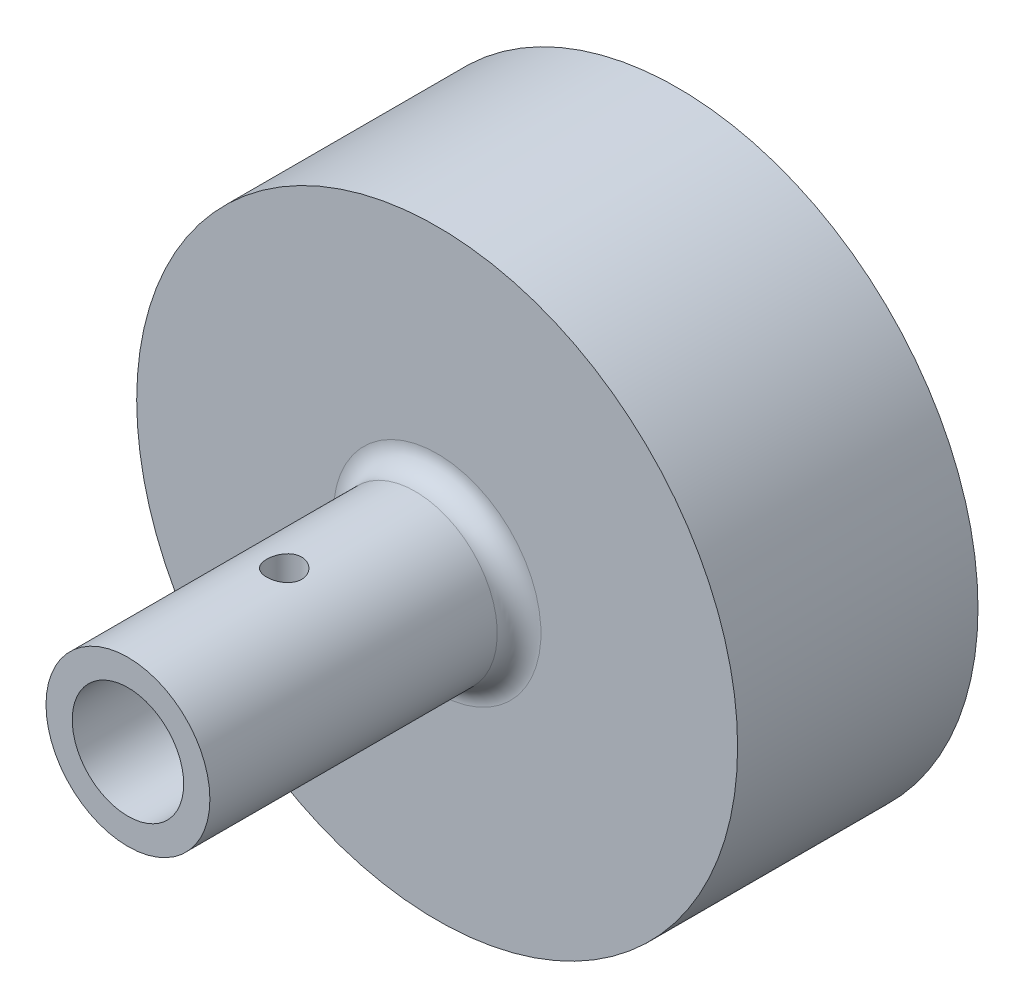
SolidWorks part; units mm, degrees
ref_plane "Front Plane" through (0, 0, 0) normal (0, 0, 1) x (1, 0, 0)
ref_plane "Top Plane" through (0, 0, 0) normal (0, 1, 0) x (1, 0, 0)
ref_plane "Right Plane" through (0, 0, 0) normal (1, 0, 0) x (0, 0, -1)
sketch "Sketch1" plane through (0, 0, 0) normal (0, 0, 1) x (1, 0, 0)
  circle A0 centre (0, 0) radius 7.5
  circle A1 centre (0, 0) radius 5.1
  dimension "D1" = 15
  dimension "D2" = 10.2
extrude "Boss-Extrude1" add sketch "Sketch1" along normal blind 28.3
sketch "Sketch4" plane through (0, 0, 0) normal (0, 0, -1) x (-1, 0, 0)
  circle A0 centre (0, 0) radius 27.5
  dimension "D1" = 55
extrude "Boss-Extrude3" add sketch "Sketch4" along normal blind 22
fillet "Fillet1" radius 2 1 edges at (7.5, 0, 0)
sketch "Sketch5" plane through (0, 0, -22) normal (0, 0, -1) x (-1, 0, 0)
  circle A8 centre (0, 12) radius 2.125
  circle A9 centre (12, 0) radius 2.125
  circle A10 centre (0, -12) radius 2.125
  circle A11 centre (-12, 0) radius 2.125
  point P11 (0, 0)
  dimension "D1" = 4.25
  dimension "D2" = 12
  dimension "D3" = 4
extrude "Cut-Extrude2" cut sketch "Sketch5" against normal blind 20
sketch "Sketch6" plane through (0, 0, 0) normal (0, 0, 1) x (1, 0, 0)
  line L0 (-3.1639, 4) -> (3.1639, 4)
  circle A0 centre (0, 0) radius 5.1 construction
  arc A1 (-3.1639, 4) -> (3.1639, 4) centre (0, 0) cw
  circle M2 centre (0, 0) radius 5.1
  dimension "D1" = 4
extrude "Boss-Extrude4" add sketch "Sketch6" along normal blind 20 contours L0 M2 region at (0, 4.4443, 0)
sketch "Sketch7" plane through (0, 0, 0) normal (0, 1, 0) x (1, 0, 0)
  line L0 (7.5, -28.3) -> (7.5, -2) construction
  line L1 (-27.5, 0) -> (27.5, 0) construction
  circle A0 centre (0, -14) radius 1.6
  dimension "D1" = 3.2
  dimension "D2" = 7.5
  dimension "D3" = 14
extrude "Cut-Extrude3" cut sketch "Sketch7" along normal through all both and the other way through all
